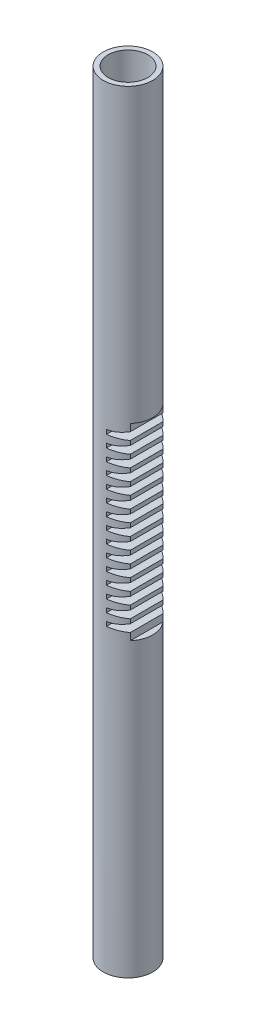
SolidWorks part; units mm, degrees
material "7075-T6 (SN)"
ref_plane "Front Plane" through (0, 0, 0) normal (0, 0, 1) x (1, 0, 0)
ref_plane "Top Plane" through (0, 0, 0) normal (0, 1, 0) x (1, 0, 0)
ref_plane "Right Plane" through (0, 0, 0) normal (1, 0, 0) x (0, 0, -1)
sketch "Sketch1" plane through (0, 0, 0) normal (0, 1, 0) x (1, 0, 0)
  circle A0 centre (0, 0) radius 12.4875
  dimension "D1" = 24.975
extrude "Boss-Extrude1" add sketch "Sketch1" along normal blind 375
sketch "Sketch2" plane through (0, 0, 0) normal (0, 0, 1) x (1, 0, 0)
  line L0 (12.4875, 187.5) -> (12.4875, 235)
  line L1 (12.4875, 0) -> (12.4875, 375) construction
  line L2 (12.4875, 187.5) -> (12.4875, 140)
  line L3 (12.4875, 140) -> (9.4, 140)
  line L4 (9.4, 140) -> (9.4, 235)
  line L5 (9.4, 235) -> (12.4875, 235)
  dimension "D1" = 47.5
  dimension "D2" = 95
extrude "Cut-Extrude1" cut sketch "Sketch2" against normal blind 29 and the other way blind 18
sketch "Sketch3" plane through (0, 0, 0) normal (0, 0, 1) x (1, 0, 0)
  line L0 (9.4, 187.5) -> (1.5, 187.5) construction
  line L1 (9.4, 235) -> (9.4, 140) construction
  line L3 (9.4, 189.4161) -> (9.4, 185.5839)
  line L4 (1.5, 186.4) -> (1.5, 188.6)
  arc A2 (1.5, 186.4) -> (9.4, 185.5839) centre (1.1958, 144.8102) cw
  arc A3 (1.5, 188.6) -> (9.4, 189.4161) centre (1.1958, 230.1898) ccw
  point P6 (1.5, 187.5)
  point P9 (1.5, 187.5)
extrude "Cut-Extrude2" cut sketch "Sketch3" against normal blind 20 and the other way blind 13
pattern_linear "LPattern1" count 8 spacing 6 along (0, 1, 0) count 8 spacing 6 along (0, -1, 0) of "Cut-Extrude2"
sketch "Sketch4" plane through (0, 0, 0) normal (0, -1, 0) x (1, 0, 0)
  circle A0 centre (0, 0) radius 10
  dimension "D1" = 20
extrude "Cut-Extrude3" cut sketch "Sketch4" against normal blind 135
sketch "Sketch5" plane through (0, 375, 0) normal (0, 1, 0) x (1, 0, 0)
  circle A0 centre (0, 0) radius 10
  dimension "D1" = 20
extrude "Cut-Extrude4" cut sketch "Sketch5" against normal blind 135
sketch "Sketch6" plane through (0, 375, 0) normal (0, 1, 0) x (1, 0, 0)
  circle A2 centre (0, 0) radius 12.4875
  circle A3 centre (0, 0) radius 12.4875
  circle A5 centre (0, 0) radius 10
  circle A6 centre (0, 0) radius 10
  dimension "D1" = 0
  dimension "D2" = 0
extrude "Boss-Extrude2" add sketch "Sketch6" along normal blind 7.5
sketch "Sketch7" plane through (0, 0, 0) normal (0, -1, 0) x (1, 0, 0)
  circle A4 centre (0, 0) radius 12.4875
  circle A5 centre (0, 0) radius 12.4875
  circle A7 centre (0, 0) radius 10
  circle A8 centre (0, 0) radius 10
  dimension "D1" = 0
  dimension "D2" = 0
extrude "Boss-Extrude3" add sketch "Sketch7" along normal blind 7.5
sketch "Sketch9" plane through (0, 0, 0) normal (0, 0, 1) x (1, 0, 0)
  line L0 (-12.4875, 139.8295) -> (-12.4875, 234.8295)
  line L1 (-12.4875, 382.5) -> (-12.4875, -7.5) construction
  line L2 (-12.4875, 234.8295) -> (-8.9875, 234.8295)
  line L3 (-8.9875, 234.8295) -> (-8.9875, 139.8295)
  line L4 (-8.9875, 139.8295) -> (-12.4875, 139.8295)
  point P5 (-12.4875, 187.3295)
extrude "Cut-Extrude5" cut sketch "Sketch9" against normal blind 10 and the other way blind 10
